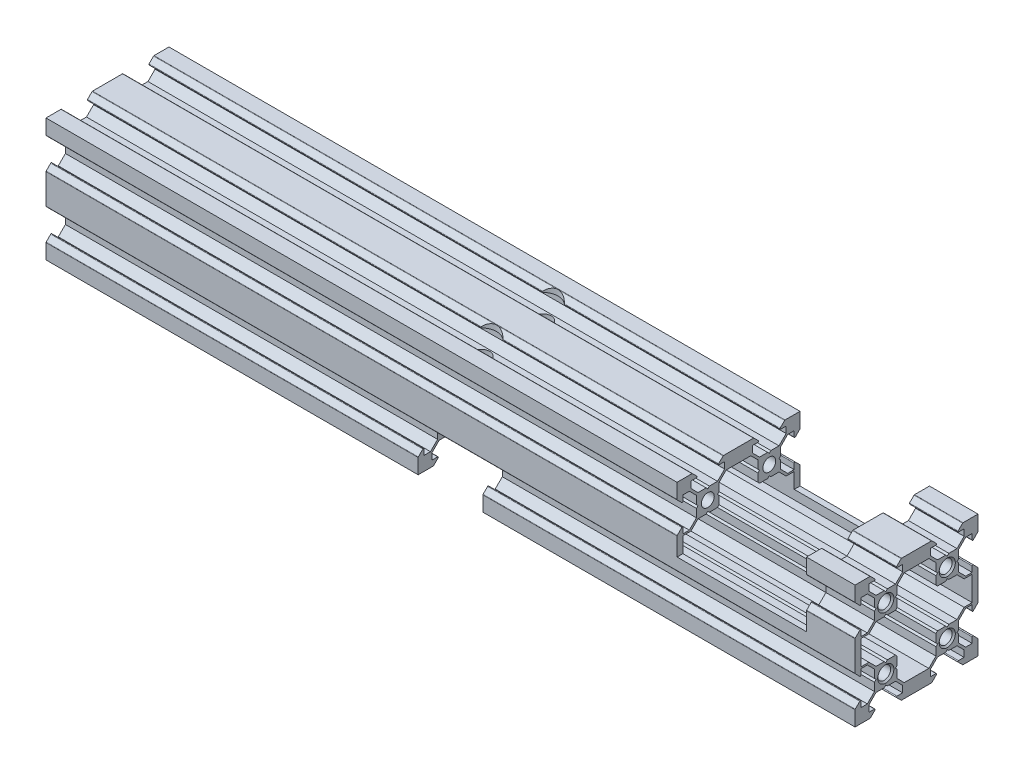
SolidWorks part; units mm, degrees
material "Alloy Steel"
ref_plane "Front Plane" through (0, 0, 0) normal (0, 0, 1) x (1, 0, 0)
ref_plane "Top Plane" through (0, 0, 0) normal (0, 1, 0) x (1, 0, 0)
ref_plane "Right Plane" through (0, 0, 0) normal (1, 0, 0) x (0, 0, -1)
sketch "Sketch2" plane through (0, 0, 0) normal (1, 0, 0) x (0, 0, -1)
  line L0 (0, 2) -> (0, 3) construction
  line L5 (0, 3) -> (-0.5, 3.5)
  line L6 (-0.5, 3.5) -> (-3.01, 3.5)
  line L7 (-3.01, 3.5) -> (-5.2091, 5.6991)
  line L8 (-5.2091, 5.6991) -> (-5.2091, 7.6991)
  line L9 (-5.2091, 7.6991) -> (-3.4791, 7.6991)
  line L10 (-3.4791, 7.6991) -> (-3.4791, 7.8991) construction
  line L11 (-3.4791, 7.8991) -> (-3.3377, 8.0405) construction
  line L12 (-3.3377, 8.0405) -> (-4.7378, 9.4406)
  line L13 (-4.7378, 9.4406) -> (-4.8792, 9.2992) construction
  line L14 (-4.8792, 9.2992) -> (-4.8792, 9.4992) construction
  line L15 (-4.8792, 9.4992) -> (-9.4992, 9.4992)
  line L16 (0, 0) -> (-9.4992, 9.4992) construction
  line L17 (0, 0) -> (-3, 0) construction
  line L18 (-9.4992, 4.8792) -> (-9.4992, 9.4992)
  line L19 (-8.0405, 3.3377) -> (-9.4406, 4.7378)
  line L20 (-7.6991, 5.2091) -> (-7.6991, 3.4791)
  line L21 (-5.6991, 5.2091) -> (-7.6991, 5.2091)
  line L22 (-3.5, 3.01) -> (-5.6991, 5.2091)
  line L23 (-3.5, 0.5) -> (-3.5, 3.01)
  line L24 (-3, 0) -> (-3.5, 0.5)
  line L25 (3, 0) -> (3.5, 0.5)
  line L26 (3.5, 0.5) -> (3.5, 3.01)
  line L27 (3.5, 3.01) -> (5.6991, 5.2091)
  line L28 (5.6991, 5.2091) -> (7.6991, 5.2091)
  line L32 (4.8792, 9.4992) -> (14.1192, 9.4992)
  line L33 (3.3377, 8.0405) -> (4.7378, 9.4406)
  line L34 (5.2091, 7.6991) -> (3.4791, 7.6991)
  line L35 (5.2091, 5.6991) -> (5.2091, 7.6991)
  line L36 (3.01, 3.5) -> (5.2091, 5.6991)
  line L37 (0.5, 3.5) -> (3.01, 3.5)
  line L38 (0, 3) -> (0.5, 3.5)
  line L39 (2, 0) -> (3, 0) construction
  line L40 (7.6991, 5.2091) -> (11.2992, 5.2091)
  line L41 (7.6991, -24.2074) -> (11.2992, -24.2074)
  line L44 (0, 0) -> (9.4992, 9.4992) construction
  line L45 (0, 0) -> (0, 3) construction
  line L46 (0, -3) -> (0.5, -3.5)
  line L47 (0.5, -3.5) -> (3.01, -3.5)
  line L51 (0, -15.9983) -> (0, -16.8134) construction
  line L53 (3.5, -3.01) -> (3.01, -3.5)
  line L54 (3.5, -15.9883) -> (3.01, -15.4983)
  line L56 (18.9983, 0) -> (18.9983, -3) construction
  line L57 (18.9983, 0) -> (20.4126, -1.4142) construction
  line L58 (3.5, -0.5) -> (3.5, -3.01)
  line L59 (3, 0) -> (3.5, -0.5)
  line L60 (0, -2) -> (0, -3) construction
  line L61 (-7.6991, -13.2992) -> (-5.2091, -13.2992)
  line L62 (-7.6991, -5.6991) -> (-7.6991, -13.2992)
  line L63 (-5.2091, -5.6991) -> (-7.6991, -5.6991)
  line L64 (28.2975, -4.8792) -> (28.4975, -4.8792) construction
  line L65 (0, 0) -> (1.4142, -1.4142) construction
  line L66 (0, 0) -> (3, 0) construction
  line L67 (-3, 0) -> (-3.5, -0.5)
  line L68 (-3.5, -0.5) -> (-3.5, -3.01)
  line L69 (-3.5, -3.01) -> (-5.6991, -5.2091)
  line L70 (-5.6991, -5.2091) -> (-7.6991, -5.2091)
  line L71 (-7.6991, -5.2091) -> (-7.6991, -3.4791)
  line L72 (-8.0405, -3.3377) -> (-9.4406, -4.7378)
  line L73 (-9.4992, -4.8792) -> (-9.4992, -14.1192)
  line L74 (28.4389, -4.7378) -> (28.2975, -4.8792) construction
  line L75 (26.8974, -3.4791) -> (27.0389, -3.3377) construction
  line L76 (26.6974, -3.4791) -> (26.8974, -3.4791) construction
  line L77 (20.9983, 0) -> (21.9983, 0) construction
  line L78 (-3.01, -3.5) -> (-5.2091, -5.6991)
  line L79 (-0.5, -3.5) -> (-3.01, -3.5)
  line L80 (0, -3) -> (-0.5, -3.5)
  line L81 (-2, 0) -> (-3, 0) construction
  line L82 (-7.6991, -3.4791) -> (-7.8991, -3.4791) construction
  line L83 (-7.8991, -3.4791) -> (-8.0405, -3.3377) construction
  line L84 (-9.4406, -4.7378) -> (-9.2992, -4.8792) construction
  line L85 (-9.2992, -4.8792) -> (-9.4992, -4.8792) construction
  line L86 (0, 0) -> (-1.4142, -1.4142) construction
  line L87 (0, 0) -> (0, -3) construction
  line L88 (18.9983, 0) -> (15.9983, 0) construction
  line L89 (-4.8792, -28.4975) -> (-9.4992, -28.4975)
  line L90 (-3.3377, -27.0389) -> (-4.7378, -28.4389)
  line L91 (-5.2091, -26.6974) -> (-3.4791, -26.6974)
  line L92 (-5.2091, -24.6974) -> (-5.2091, -26.6974)
  line L93 (-9.4992, -23.8775) -> (-9.4992, -28.4975)
  line L94 (-8.0405, -22.336) -> (-9.4406, -23.7361)
  line L95 (-7.6991, -24.2074) -> (-7.6991, -22.4774)
  line L96 (-5.6991, -24.2074) -> (-7.6991, -24.2074)
  line L97 (5.2091, -26.6974) -> (3.4791, -26.6974)
  line L98 (3.3377, -27.0389) -> (4.7378, -28.4389)
  line L99 (4.8792, -28.4975) -> (14.1192, -28.4975)
  line L103 (5.6991, -24.2074) -> (7.6991, -24.2074)
  line L104 (5.2091, -24.6974) -> (5.2091, -26.6974)
  line L105 (3.01, -22.4983) -> (5.2091, -24.6974)
  line L106 (3.5, -22.0083) -> (5.6991, -24.2074)
  line L107 (-3.5, -22.0083) -> (-5.6991, -24.2074)
  line L108 (-3.01, -22.4983) -> (-5.2091, -24.6974)
  line L109 (-0.5, -22.4983) -> (-3.01, -22.4983)
  line L110 (0, -21.9983) -> (0.5, -22.4983)
  line L111 (0, -21.9983) -> (-0.5, -22.4983)
  line L112 (0.5, -22.4983) -> (3.01, -22.4983)
  line L113 (3.5, -19.4983) -> (3.5, -22.0083)
  line L114 (-3.5, -19.4983) -> (-3.5, -22.0083)
  line L115 (-3, -18.9983) -> (-3.5, -19.4983)
  line L116 (-3, -18.9983) -> (-3.5, -18.4983)
  line L117 (3, -18.9983) -> (3.5, -19.4983)
  line L118 (3, -18.9983) -> (3.5, -18.4983)
  line L119 (3.5, -18.4983) -> (3.5, -15.9883)
  line L121 (18.9983, 0) -> (17.5841, -1.4142) construction
  line L122 (18.9983, -2) -> (18.9983, -3) construction
  line L123 (18.9983, -15.9983) -> (18.9983, -16.8134) construction
  line L124 (18.9983, 0) -> (18.9983, 3) construction
  line L125 (18.9983, 0) -> (9.4992, 9.4992) construction
  line L128 (-5.6991, -13.7892) -> (-7.6991, -13.7892)
  line L129 (-7.6991, -13.7892) -> (-7.6991, -15.5192)
  line L130 (-8.0405, -15.6607) -> (-9.4406, -14.2606)
  line L132 (16.9983, 0) -> (15.9983, 0) construction
  line L133 (18.9983, 0) -> (21.9983, 0) construction
  line L134 (-3.01, -15.4983) -> (-5.2091, -13.2992)
  line L135 (-3.5, -15.9883) -> (-5.6991, -13.7892)
  line L136 (-3.5, -18.4983) -> (-3.5, -15.9883)
  line L137 (-0.5, -15.4983) -> (-3.01, -15.4983)
  line L138 (0, -15.9983) -> (-0.5, -15.4983)
  line L139 (0, -15.9983) -> (0.5, -15.4983)
  line L140 (0.5, -15.4983) -> (3.01, -15.4983)
  line L141 (18.9983, 0) -> (28.4975, 9.4992) construction
  line L142 (23.8775, 9.2992) -> (23.8775, 9.4992) construction
  line L143 (23.7361, 9.4406) -> (23.8775, 9.2992) construction
  line L144 (22.4774, 7.8991) -> (22.336, 8.0405) construction
  line L145 (22.4774, 7.6991) -> (22.4774, 7.8991) construction
  line L146 (18.9983, 2) -> (18.9983, 3) construction
  line L147 (18.4983, -15.4983) -> (15.9883, -15.4983)
  line L148 (18.9983, -15.9983) -> (18.4983, -15.4983)
  line L149 (18.9983, -15.9983) -> (19.4983, -15.4983)
  line L150 (19.4983, -15.4983) -> (22.0083, -15.4983)
  line L151 (22.4983, -18.4983) -> (22.4983, -15.9883)
  line L152 (22.4983, -15.9883) -> (24.6974, -13.7892)
  line L153 (22.0083, -15.4983) -> (24.2074, -13.2992)
  line L154 (27.0389, -15.6607) -> (28.4389, -14.2606)
  line L155 (26.6974, -13.7892) -> (26.6974, -15.5192)
  line L156 (24.6974, -13.7892) -> (26.6974, -13.7892)
  line L157 (15.4983, -18.4983) -> (15.4983, -15.9883)
  line L158 (15.9983, -18.9983) -> (15.4983, -18.4983)
  line L159 (15.9983, -18.9983) -> (15.4983, -19.4983)
  line L160 (21.9983, -18.9983) -> (22.4983, -18.4983)
  line L161 (21.9983, -18.9983) -> (22.4983, -19.4983)
  line L162 (22.4983, -19.4983) -> (22.4983, -22.0083)
  line L163 (15.4983, -19.4983) -> (15.4983, -22.0083)
  line L164 (18.4983, -22.4983) -> (15.9883, -22.4983)
  line L165 (18.9983, -21.9983) -> (19.4983, -22.4983)
  line L166 (18.9983, -21.9983) -> (18.4983, -22.4983)
  line L167 (19.4983, -22.4983) -> (22.0083, -22.4983)
  line L168 (22.0083, -22.4983) -> (24.2074, -24.6974)
  line L169 (22.4983, -22.0083) -> (24.6974, -24.2074)
  line L170 (15.4983, -22.0083) -> (13.2992, -24.2074)
  line L171 (15.9883, -22.4983) -> (13.7892, -24.6974)
  line L172 (13.7892, -24.6974) -> (13.7892, -26.6974)
  line L173 (13.2992, -24.2074) -> (11.2992, -24.2074)
  line L176 (15.6607, -27.0389) -> (14.2606, -28.4389)
  line L177 (13.7892, -26.6974) -> (15.5192, -26.6974)
  line L178 (24.6974, -24.2074) -> (26.6974, -24.2074)
  line L179 (26.6974, -24.2074) -> (26.6974, -22.4774)
  line L180 (27.0389, -22.336) -> (28.4389, -23.7361)
  line L181 (28.4975, -23.8775) -> (28.4975, -28.4975)
  line L182 (24.2074, -24.6974) -> (24.2074, -26.6974)
  line L183 (24.2074, -26.6974) -> (22.4774, -26.6974)
  line L184 (22.336, -27.0389) -> (23.7361, -28.4389)
  line L185 (23.8775, -28.4975) -> (28.4975, -28.4975)
  line L186 (18.9983, -3) -> (19.4983, -3.5)
  line L187 (19.4983, -3.5) -> (22.0083, -3.5)
  line L188 (22.0083, -3.5) -> (24.2074, -5.6991)
  line L189 (28.4975, -4.8792) -> (28.4975, -14.1192)
  line L190 (27.0389, -3.3377) -> (28.4389, -4.7378)
  line L191 (26.6974, -5.2091) -> (26.6974, -3.4791)
  line L192 (24.6974, -5.2091) -> (26.6974, -5.2091)
  line L193 (22.4983, -3.01) -> (24.6974, -5.2091)
  line L194 (22.4983, -0.5) -> (22.4983, -3.01)
  line L195 (21.9983, 0) -> (22.4983, -0.5)
  line L196 (24.2074, -5.6991) -> (26.6974, -5.6991)
  line L197 (26.6974, -5.6991) -> (26.6974, -13.2992)
  line L198 (26.6974, -13.2992) -> (24.2074, -13.2992)
  line L199 (15.9983, 0) -> (15.4983, -0.5)
  line L200 (15.4983, -0.5) -> (15.4983, -3.01)
  line L201 (15.4983, -15.9883) -> (15.9883, -15.4983)
  line L202 (15.4983, -3.01) -> (15.9883, -3.5)
  line L203 (18.4983, -3.5) -> (15.9883, -3.5)
  line L204 (18.9983, -3) -> (18.4983, -3.5)
  line L205 (18.9983, 3) -> (18.4983, 3.5)
  line L206 (18.4983, 3.5) -> (15.9883, 3.5)
  line L207 (15.9883, 3.5) -> (13.7892, 5.6991)
  line L208 (13.7892, 5.6991) -> (13.7892, 7.6991)
  line L209 (13.7892, 7.6991) -> (15.5192, 7.6991)
  line L210 (15.6607, 8.0405) -> (14.2606, 9.4406)
  line L213 (13.2992, 5.2091) -> (11.2992, 5.2091)
  line L214 (15.4983, 3.01) -> (13.2992, 5.2091)
  line L215 (15.4983, 0.5) -> (15.4983, 3.01)
  line L216 (15.9983, 0) -> (15.4983, 0.5)
  line L217 (21.9983, 0) -> (22.4983, 0.5)
  line L218 (22.4983, 0.5) -> (22.4983, 3.01)
  line L219 (22.4983, 3.01) -> (24.6974, 5.2091)
  line L220 (24.6974, 5.2091) -> (26.6974, 5.2091)
  line L221 (26.6974, 5.2091) -> (26.6974, 3.4791)
  line L222 (27.0389, 3.3377) -> (28.4389, 4.7378)
  line L223 (28.4975, 4.8792) -> (28.4975, 9.4992)
  line L224 (23.8775, 9.4992) -> (28.4975, 9.4992)
  line L225 (22.336, 8.0405) -> (23.7361, 9.4406)
  line L226 (24.2074, 7.6991) -> (22.4774, 7.6991)
  line L227 (24.2074, 5.6991) -> (24.2074, 7.6991)
  line L228 (22.0083, 3.5) -> (24.2074, 5.6991)
  line L229 (19.4983, 3.5) -> (22.0083, 3.5)
  line L230 (18.9983, 3) -> (19.4983, 3.5)
  circle A0 centre (0, 0) radius 2
  arc A1 (-3.3377, 8.0405) -> (-3.4791, 7.6991) centre (-3.4791, 7.8991) cw
  arc A2 (-4.7378, 9.4406) -> (-4.8792, 9.4992) centre (-4.8792, 9.2992) ccw
  arc A3 (-9.4406, 4.7378) -> (-9.4992, 4.8792) centre (-9.2992, 4.8792) cw
  arc A4 (-8.0405, 3.3377) -> (-7.6991, 3.4791) centre (-7.8991, 3.4791) ccw
  arc A7 (4.7378, 9.4406) -> (4.8792, 9.4992) centre (4.8792, 9.2992) cw
  arc A8 (3.3377, 8.0405) -> (3.4791, 7.6991) centre (3.4791, 7.8991) ccw
  circle A9 centre (18.9983, -18.9983) radius 2
  arc A10 (28.4389, -14.2606) -> (28.4975, -14.1192) centre (28.2975, -14.1192) ccw
  arc A11 (27.0389, -15.6607) -> (26.6974, -15.5192) centre (26.8974, -15.5192) cw
  arc A13 (-8.0405, -3.3377) -> (-7.6991, -3.4791) centre (-7.8991, -3.4791) cw
  arc A14 (-9.4406, -4.7378) -> (-9.4992, -4.8792) centre (-9.2992, -4.8792) ccw
  arc A16 (14.2606, -28.4389) -> (14.1192, -28.4975) centre (14.1192, -28.2975) cw
  arc A17 (-4.7378, -28.4389) -> (-4.8792, -28.4975) centre (-4.8792, -28.2975) cw
  arc A18 (-3.3377, -27.0389) -> (-3.4791, -26.6974) centre (-3.4791, -26.8974) ccw
  arc A19 (-9.4406, -23.7361) -> (-9.4992, -23.8775) centre (-9.2992, -23.8775) ccw
  arc A20 (-8.0405, -22.336) -> (-7.6991, -22.4774) centre (-7.8991, -22.4774) cw
  arc A21 (3.3377, -27.0389) -> (3.4791, -26.6974) centre (3.4791, -26.8974) cw
  arc A22 (4.7378, -28.4389) -> (4.8792, -28.4975) centre (4.8792, -28.2975) ccw
  arc A25 (15.6607, -27.0389) -> (15.5192, -26.6974) centre (15.5192, -26.8974) ccw
  arc A26 (27.0389, -22.336) -> (26.6974, -22.4774) centre (26.8974, -22.4774) ccw
  arc A27 (28.4389, -23.7361) -> (28.4975, -23.8775) centre (28.2975, -23.8775) cw
  arc A28 (22.336, -27.0389) -> (22.4774, -26.6974) centre (22.4774, -26.8974) cw
  arc A29 (23.7361, -28.4389) -> (23.8775, -28.4975) centre (23.8775, -28.2975) ccw
  arc A30 (-8.0405, -15.6607) -> (-7.6991, -15.5192) centre (-7.8991, -15.5192) ccw
  arc A31 (-9.4406, -14.2606) -> (-9.4992, -14.1192) centre (-9.2992, -14.1192) cw
  arc A32 (28.4389, -4.7378) -> (28.4975, -4.8792) centre (28.2975, -4.8792) cw
  circle A33 centre (0, -18.9983) radius 2
  arc A34 (27.0389, -3.3377) -> (26.6974, -3.4791) centre (26.8974, -3.4791) ccw
  arc A35 (15.6607, 8.0405) -> (15.5192, 7.6991) centre (15.5192, 7.8991) cw
  arc A36 (14.2606, 9.4406) -> (14.1192, 9.4992) centre (14.1192, 9.2992) ccw
  arc A39 (27.0389, 3.3377) -> (26.6974, 3.4791) centre (26.8974, 3.4791) cw
  arc A40 (28.4389, 4.7378) -> (28.4975, 4.8792) centre (28.2975, 4.8792) ccw
  arc A41 (23.7361, 9.4406) -> (23.8775, 9.4992) centre (23.8775, 9.2992) cw
  arc A42 (22.336, 8.0405) -> (22.4774, 7.6991) centre (22.4774, 7.8991) ccw
  circle A43 centre (18.9983, 0) radius 2
  point P0 (0, 0)
  point P22 (0, 0)
  point P64 (0, 0)
  point P93 (0, 0)
  point P122 (0, 0)
  point P287 (18.9983, 0)
  point P288 (18.9983, 0)
  point P289 (18.9983, 0)
  point P290 (18.9983, 0)
  point P291 (18.9983, 0)
extrude "Main Body" add sketch "Sketch2" along normal blind 125 and the other way blind 125 contours L78 L79 L80 L46 L47 L58 L59 L25 L26 L27 L28 L32 A7 L33 A8 L34 L35 L36 L37 L38 L5 L6 L7 L8 L9 A1 L12 A2 region at (0, 2.87, -0.63)
chamfer "Chamfer1" distance 0.5 angle 45 1 edges at (125, 0, -2)
chamfer "Chamfer2" distance 0.5 angle 45 1 edges at (-125, 0, -2)
chamfer "Chamfer3" distance 0.5 angle 45 6 edges at (-125, -18.9983, -2) (-125, -18.9983, -20.9983) (-125, 0, -20.9983) (125, -18.9983, -2) (125, -18.9983, -20.9983) (125, 0, -20.9983)
sketch "Sketch5" plane through (0, 0, 0) normal (0, 1, 0) x (1, 0, 0)
  line L0 (-125, 18.9983) -> (125, 18.9983) construction
  circle A0 centre (0, 18.9983) radius 2.6
  circle A1 centre (0, 0) radius 2.6
  dimension "D1" = 5.2
  dimension "D2" = 5.2
extrude "Top Holes" cut sketch "Sketch5" against normal through all both and the other way through all
sketch "Sketch6" plane through (0, 9.4992, 0) normal (0, 1, 0) x (1, 0, 0)
  circle A0 centre (0, 18.9983) radius 4.75
  circle A1 centre (0, 0) radius 4.75
  dimension "D1" = 9.5
  dimension "D2" = 9.5
extrude "Top Hole Clearance" cut sketch "Sketch6" against normal blind 3 and the other way through all
sketch "Sketch7" plane through (0, 0, 0) normal (0, 0, 1) x (1, 0, 0)
  line L0 (-125, -28.4975) -> (125, -28.4975) construction
  line L1 (-10, -28.4975) -> (10, -28.4975)
  line L14 (-10, -28.4975) -> (-10, -18.9983)
  line L15 (-125, -18.9983) -> (125, -18.9983) construction
  line L16 (-10, -18.9983) -> (10, -18.9983)
  line L17 (10, -18.9983) -> (10, -28.4975)
  line L18 (-125, 9.4992) -> (125, 9.4992) construction
  line L19 (110, 9.4992) -> (70, 9.4992)
  line L20 (110, 9.4992) -> (110, -10.5008)
  line L21 (110, -10.5008) -> (70, -10.5008)
  line L22 (70, 9.4992) -> (70, -10.5008)
  dimension "D1" = 10
  dimension "D2" = 10
  dimension "D3" = 70
  dimension "D4" = 110
  dimension "D5" = 20
extrude "Cut-Extrude5" cut sketch "Sketch7" against normal through all both and the other way through all
